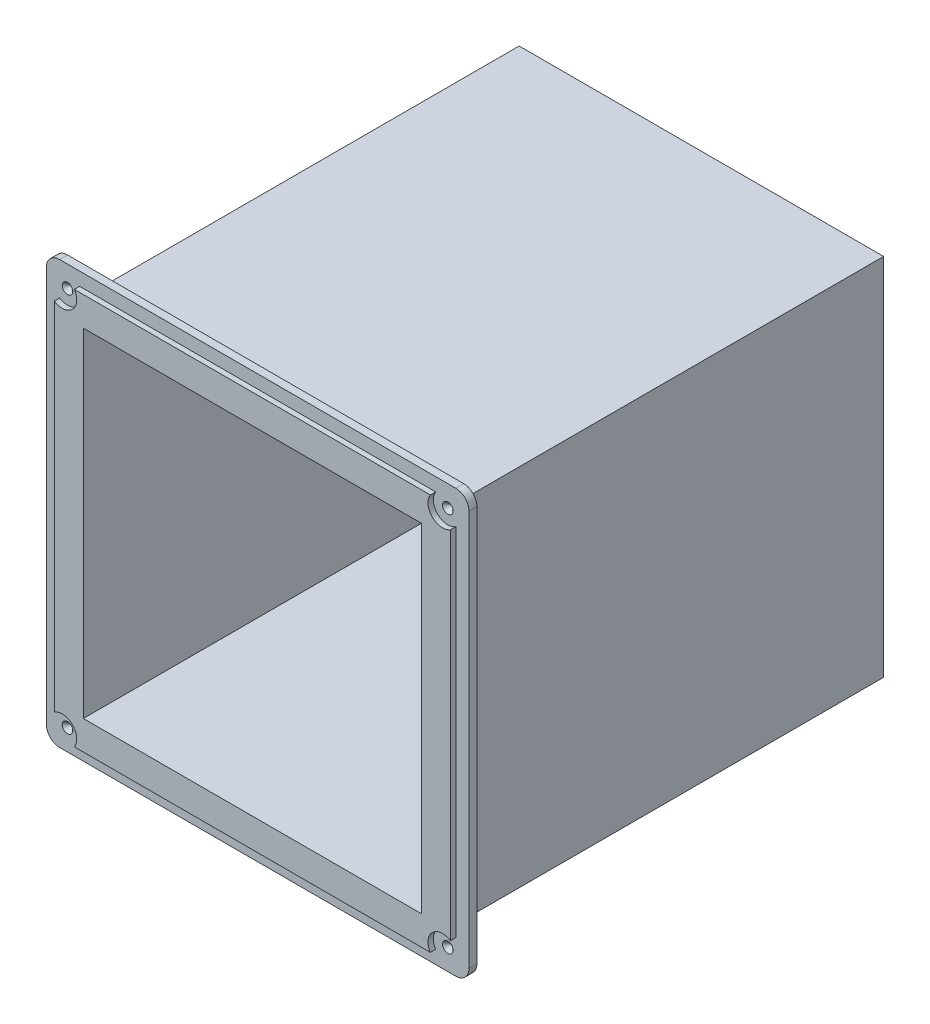
SolidWorks part; units mm, degrees
ref_plane "Ön Düzlem" through (0, 0, 0) normal (0, 0, 1) x (1, 0, 0)
ref_plane "Üst Düzlem" through (0, 0, 0) normal (0, 1, 0) x (1, 0, 0)
ref_plane "Sağ Düzlem" through (0, 0, 0) normal (1, 0, 0) x (0, 0, -1)
sketch "Çizim1" plane through (0, 0, 0) normal (0, 0, 1) x (1, 0, 0)
  line L0 (0, 53.6445) -> (0, -46.8604) construction
  line L1 (-88.1931, 0) -> (105.279, 0) construction
  line L11 (-37.5, 40) -> (37.5, 40)
  line L12 (-40, 37.5) -> (-40, -37.5)
  line L13 (-37.5, -40) -> (37.5, -40)
  line L14 (40, 37.5) -> (40, -37.5)
  arc A0 (-40, -37.5) -> (-37.5, -40) centre (-37.5, -37.5) ccw
  arc A1 (37.5, -40) -> (40, -37.5) centre (37.5, -37.5) ccw
  arc A2 (37.5, 40) -> (40, 37.5) centre (37.5, 37.5) cw
  arc A3 (-37.5, 40) -> (-40, 37.5) centre (-37.5, 37.5) ccw
  dimension "D2" = 2.5
  dimension "D9" = 40
  dimension "D10" = 80
  dimension "D11" = 40
  dimension "D12" = 80
extrude "Yükseklik-Ekstrüzyon1" add sketch "Çizim1" along normal blind 1.5
sketch "Çizim2" plane through (0, 0, 1.5) normal (0, 0, 1) x (1, 0, 0)
  line L0 (0, 20.5344) -> (0, -17.8448) construction
  line L1 (0, 0) -> (28.0344, 0) construction
  line L3 (-37.5, 37.5) -> (37.5, 37.5)
  line L4 (-37.5, 37.5) -> (-37.5, -37.5)
  line L5 (-37.5, -37.5) -> (37.5, -37.5)
  line L6 (37.5, 37.5) -> (37.5, -37.5)
  dimension "D1" = 37.5
  dimension "D2" = 75
  dimension "D3" = 37.5
  dimension "D4" = 75
extrude "Yükseklik-Ekstrüzyon2" add sketch "Çizim2" along normal blind 1
sketch "Çizim3" plane through (0, 0, 2.5) normal (0, 0, 1) x (1, 0, 0)
  line L0 (0, 25.1896) -> (0, -13.9138) construction
  line L1 (-18.1034, 0) -> (29.4827, 0) construction
  line L3 (-32, 32) -> (32, 32)
  line L4 (-32, 32) -> (-32, -32)
  line L5 (-32, -32) -> (32, -32)
  line L6 (32, 32) -> (32, -32)
  dimension "D1" = 32
  dimension "D2" = 64
  dimension "D3" = 32
  dimension "D4" = 64
extrude "Kes-Ekstrüzyon1" cut sketch "Çizim3" against normal blind 41
sketch "Çizim4" plane through (0, 0, 0) normal (0, 0, -1) x (-1, 0, 0)
  line L1 (-32, 32) -> (32, 32)
  line L2 (-32, 32) -> (-32, -32)
  line L3 (-32, -32) -> (32, -32)
  line L4 (32, 32) -> (32, -32)
  line L5 (-34.5, 34.5) -> (34.5, 34.5)
  line L6 (-34.5, 34.5) -> (-34.5, -34.5)
  line L7 (-34.5, -34.5) -> (34.5, -34.5)
  line L8 (34.5, 34.5) -> (34.5, -34.5)
  dimension "D1" = 2.5
  dimension "D2" = 2.5
  dimension "D3" = 2.5
  dimension "D4" = 2.5
extrude "Yükseklik-Ekstrüzyon4" add sketch "Çizim4" along normal blind 80
sketch "Çizim5" plane through (0, 0, -80) normal (0, 0, -1) x (-1, 0, 0)
  line L1 (-34.5, 34.5) -> (34.5, 34.5)
  line L2 (-34.5, 34.5) -> (-34.5, -34.5)
  line L3 (-34.5, -34.5) -> (34.5, -34.5)
  line L4 (34.5, 34.5) -> (34.5, -34.5)
extrude "Yükseklik-Ekstrüzyon5" add sketch "Çizim5" along normal blind 2.5
sketch "Çizim6" plane through (0, 0, -82.5) normal (0, 0, -1) x (-1, 0, 0)
  line L0 (-34.5, -34.5) -> (34.5, -34.5) construction
  line L1 (-19.5, -34.5) -> (-9.5, -34.5)
  line L2 (-19.5, -34.5) -> (-19.5, -19.5)
  line L3 (-19.5, -19.5) -> (-9.5, -19.5)
  line L4 (-9.5, -34.5) -> (-9.5, -19.5)
  line L5 (-34.5, 34.5) -> (-34.5, -34.5) construction
  dimension "D1" = 15
  dimension "D2" = 15
  dimension "D3" = 10
extrude "Kes-Ekstrüzyon2" cut sketch "Çizim6" against normal blind 60
sketch "Çizim7" plane through (0, 0, -80) normal (0, 0, 1) x (1, 0, 0)
  line L0 (0, 20.3275) -> (0, -16.8103) construction
  line L1 (21.3103, 0) -> (-18.931, 0) construction
  line L3 (-25.85, 25) -> (25.85, 25)
  line L4 (-25.85, 25) -> (-25.85, -25)
  line L5 (-25.85, -25) -> (25.85, -25)
  line L6 (25.85, 25) -> (25.85, -25)
  line L7 (-27, 17) -> (27, 17)
  line L8 (-27, 17) -> (-27, -17)
  line L9 (-27, -17) -> (27, -17)
  line L10 (27, 17) -> (27, -17)
  circle A0 centre (-25.85, 25) radius 2.75
  circle A1 centre (-27, 17) radius 2.75
  circle A2 centre (-25.85, 25) radius 1
  circle A3 centre (-27, 17) radius 1
  circle A4 centre (27, 17) radius 1
  circle A5 centre (27, 17) radius 2.75
  circle A6 centre (25.85, 25) radius 1
  circle A7 centre (25.85, 25) radius 2.75
  circle A8 centre (25.85, -25) radius 1
  circle A9 centre (25.85, -25) radius 2.75
  circle A10 centre (27, -17) radius 1
  circle A11 centre (27, -17) radius 2.75
  circle A12 centre (-27, -17) radius 1
  circle A13 centre (-27, -17) radius 2.75
  circle A14 centre (-25.85, -25) radius 1
  circle A15 centre (-25.85, -25) radius 2.75
  dimension "D5" = 5.5
  dimension "D10" = 5.5
  dimension "D11" = 2
  dimension "D12" = 2
  dimension "D2" = 25
  dimension "D3" = 25.85
  dimension "D4" = 17
  dimension "D6" = 27
extrude "Yükseklik-Ekstrüzyon7" add sketch "Çizim7" along normal blind 10 contours A0 | A2 | A1 | A3 | A7 | A6 | A5 | A4 | A11 | A10 | A13 | A12 | A15 | A14 | A9 | A8
chamfer "Pah2" distance 1.5 angle 45 8 edges at (23.1, -25, -80) (24.25, -17, -80) (-28.6, -25, -80) (-29.75, -17, -80) (-29.75, 17, -80) (-28.6, 25, -80) (24.25, 17, -80) (23.1, 25, -80)
sketch "Çizim8" plane through (0, 0, 2.5) normal (0, 0, 1) x (1, 0, 0)
  line L0 (37.5, 40) -> (-37.5, 40) construction
  line L1 (-32, 32) -> (-40, 32) construction
  line L2 (-32, 32) -> (-32, 40) construction
  line L3 (-32, 40) -> (-40, 40) construction
  line L4 (-40, 32) -> (-40, 40) construction
  line L5 (-40, 37.5) -> (-40, -37.5) construction
  line L6 (-40, 40) -> (-32, 32) construction
  line L7 (-32, 40) -> (-40, 32) construction
  line L8 (0, 25.8534) -> (0, -17.4675) construction
  line L9 (-10.1206, 0) -> (16.9158, 0) construction
  circle A0 centre (-36, 36) radius 2.75
  circle A3 centre (36, 36) radius 2.75
  circle A5 centre (36, -36) radius 2.75
  circle A7 centre (-36, -36) radius 2.75
  dimension "D1" = 5.5
extrude "Kes-Ekstrüzyon4" cut sketch "Çizim8" against normal blind 1
sketch "Çizim10" plane through (0, 0, 1.5) normal (0, 0, 1) x (1, 0, 0)
  line L0 (37.5, 40) -> (-37.5, 40) construction
  line L1 (-32, 32) -> (-40, 32) construction
  line L2 (-32, 32) -> (-32, 40) construction
  line L3 (-32, 40) -> (-40, 40) construction
  line L4 (-40, 32) -> (-40, 40) construction
  line L5 (-40, 37.5) -> (-40, -37.5) construction
  line L6 (-32, 32) -> (-40, 40) construction
  line L7 (-32, 40) -> (-40, 32) construction
  line L8 (0, 28.0047) -> (0, 0) construction
  line L9 (-13.2538, 0) -> (15.3112, 0) construction
  circle A0 centre (-36, 36) radius 1
  circle A1 centre (36, 36) radius 1
  circle A2 centre (36, -36) radius 1
  circle A3 centre (-36, -36) radius 1
  dimension "D1" = 2
extrude "Kes-Ekstrüzyon6" cut sketch "Çizim10" against normal blind 1.5 draft 45
